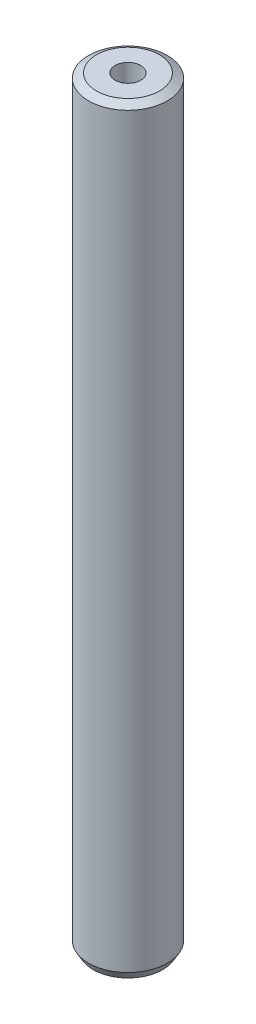
SolidWorks part; units mm, degrees
ref_plane "Front Plane" through (0, 0, 0) normal (0, 0, 1) x (1, 0, 0)
ref_plane "Top Plane" through (0, 0, 0) normal (0, 1, 0) x (1, 0, 0)
ref_plane "Right Plane" through (0, 0, 0) normal (1, 0, 0) x (0, 0, -1)
sketch "Sketch1" plane through (0, 0, 0) normal (0, 1, 0) x (1, 0, 0)
  circle A0 centre (0, 0) radius 10
  dimension "SHAFT_OD" = 20
extrude "Boss-Extrude1" add sketch "Sketch1" along normal blind 192.7519
sketch "Sketch2" plane through (0, 0, 0) normal (0, 1, 0) x (1, 0, 0)
  circle A0 centre (0, 0) radius 3.25
  dimension "BORE_D" = 6.5
extrude "Cut-Extrude1" cut sketch "Sketch2" along normal through all
chamfer "Chamfer1" distance 1.1664 angle 60 2 edges at (0, 192.7519, 10) (0, 0, 10) first distance on face at (0, 192.7519, 10) first distance on face at (0, 0, 3.25)
